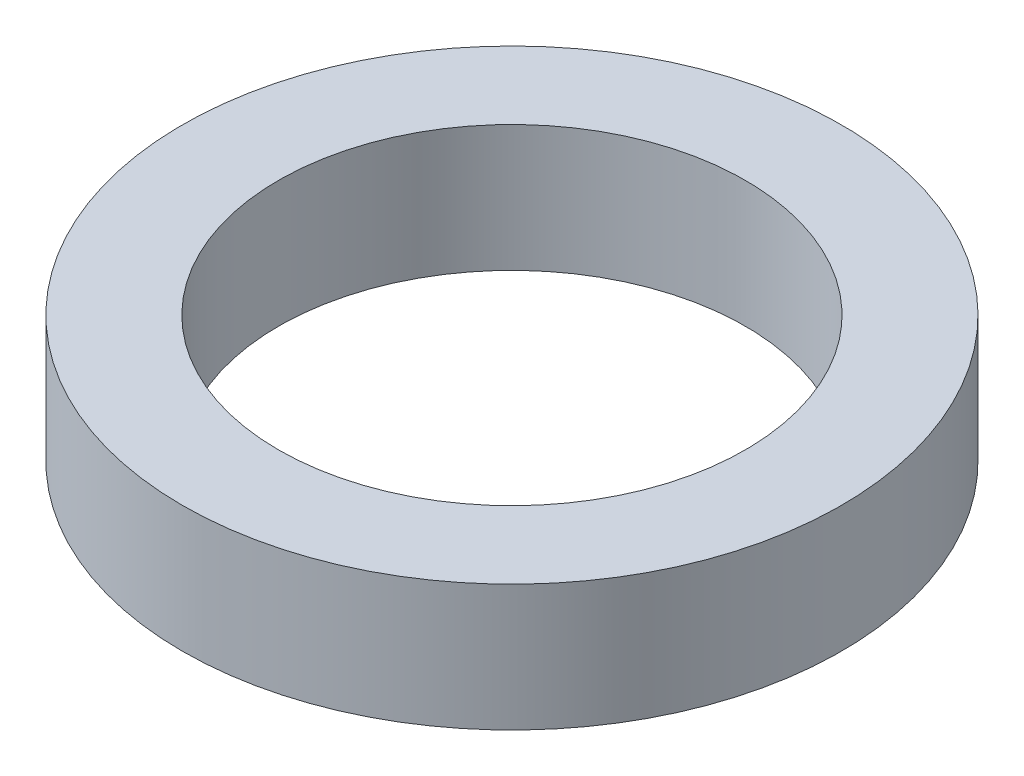
SolidWorks part; units mm, degrees
ref_plane "Front Plane" through (0, 0, 0) normal (0, 0, 1) x (1, 0, 0)
ref_plane "Top Plane" through (0, 0, 0) normal (0, 1, 0) x (1, 0, 0)
ref_plane "Right Plane" through (0, 0, 0) normal (1, 0, 0) x (0, 0, -1)
sketch "Sketch1" plane through (0, 0, 0) normal (0, 1, 0) x (1, 0, 0)
  circle A0 centre (0, 0) radius 60
  dimension "FLANGE_OD" = 120
extrude "Boss-Extrude1" add sketch "Sketch1" along normal blind 23
sketch "Sketch2" plane through (0, 0, 0) normal (0, 1, 0) x (1, 0, 0)
  circle A0 centre (0, 0) radius 42.5
  dimension "BORE_D" = 85
extrude "Cut-Extrude1" cut sketch "Sketch2" along normal through all
sketch "Sketch3" plane through (0, 23, 0) normal (0, 1, 0) x (1, 0, 0)
  circle A0 centre (0, 0) radius 24.8997 construction
  circle A1 centre (-24.8997, 0) radius 2.0678
  dimension "BOLT_D" = 4.1356
  dimension "BOLT_PCD" = 49.7993
extrude "Cut-Extrude2" cut sketch "Sketch3" against normal blind 14.8569 rebuild error yes
pattern_circular "CirPattern1" count 6 over 360 rebuild error yes
